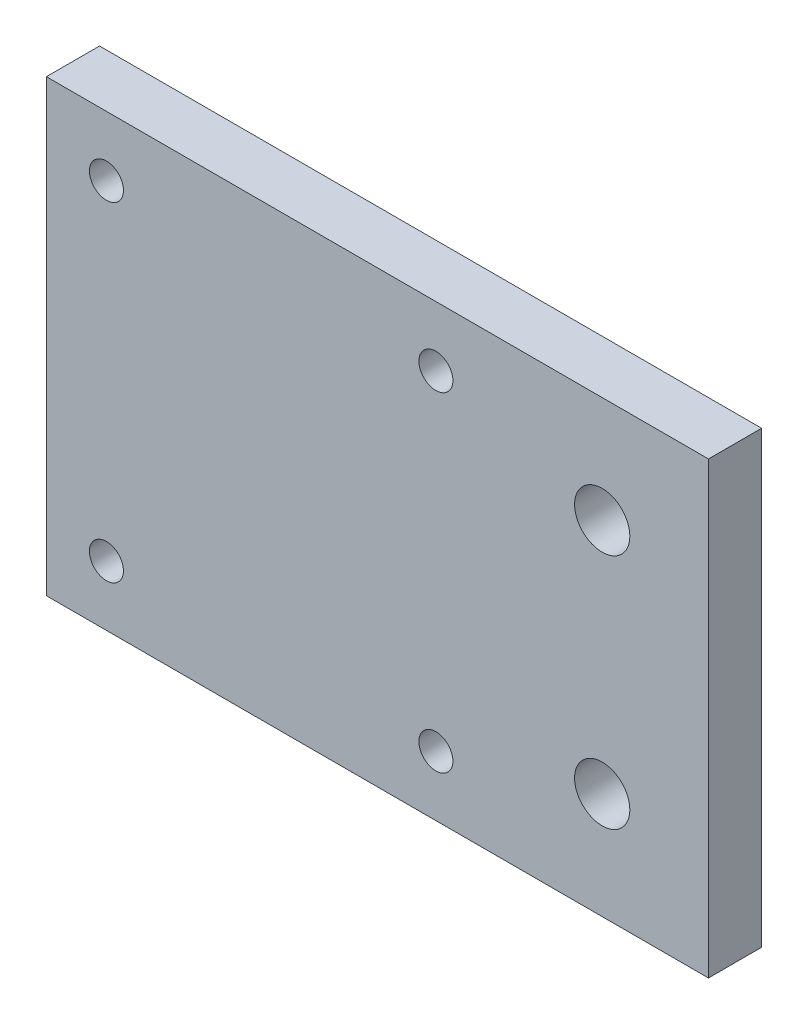
SolidWorks part; units mm, degrees
material "PET"
ref_plane "Front Plane" through (0, 0, 0) normal (0, 0, 1) x (1, 0, 0)
ref_plane "Top Plane" through (0, 0, 0) normal (0, 1, 0) x (1, 0, 0)
ref_plane "Right Plane" through (0, 0, 0) normal (1, 0, 0) x (0, 0, -1)
sketch "Sketch2" plane through (0, 0, 0) normal (0, 0, 1) x (1, 0, 0)
  line L0 (-21.15, 21.15) -> (21.15, -21.15) construction
  line L1 (-21.15, 21.15) -> (21.15, 21.15)
  line L2 (-21.15, 21.15) -> (-21.15, -21.15)
  line L3 (-21.15, -21.15) -> (21.15, -21.15)
  line L4 (21.15, 21.15) -> (21.15, -21.15)
  line L5 (21.15, 21.15) -> (41.15, 21.15)
  line L6 (21.15, 21.15) -> (21.15, -21.15)
  line L7 (21.15, -21.15) -> (41.15, -21.15)
  line L8 (41.15, 21.15) -> (41.15, -21.15)
  line L9 (31.15, 21.15) -> (31.15, -21.15) construction
  line L10 (-15.5, -15.5) -> (15.5, 15.5) construction
  circle A0 centre (31.15, 11.15) radius 2.6
  circle A1 centre (31.15, -11.15) radius 2.6
  circle A2 centre (-15.5, 15.5) radius 1.6
  circle A3 centre (15.5, -15.5) radius 1.6
  circle A4 centre (15.5, 15.5) radius 1.6
  circle A5 centre (-15.5, -15.5) radius 1.6
  point P21 (-11.9276, 11.9276)
  dimension "D4" = 5.2
  dimension "D5" = 5.2
  dimension "D8" = 3.2
  dimension "D9" = 3.2
  dimension "D10" = 3.2
  dimension "D11" = 3.2
  dimension "D1" = 20
  dimension "D2" = 42.3
  dimension "D3" = 42.3
  dimension "D6" = 10
  dimension "D7" = 10
  dimension "D12" = 31
  dimension "D13" = 31
extrude "Boss-Extrude1" add sketch "Sketch2" along normal blind 5 contours L4 L1 L2 L3 A5 A4 A3 A2 | L8 L5 L4 L7 A1 A0 region at (0, 0, 0) region at (31.15, 0, 0)
